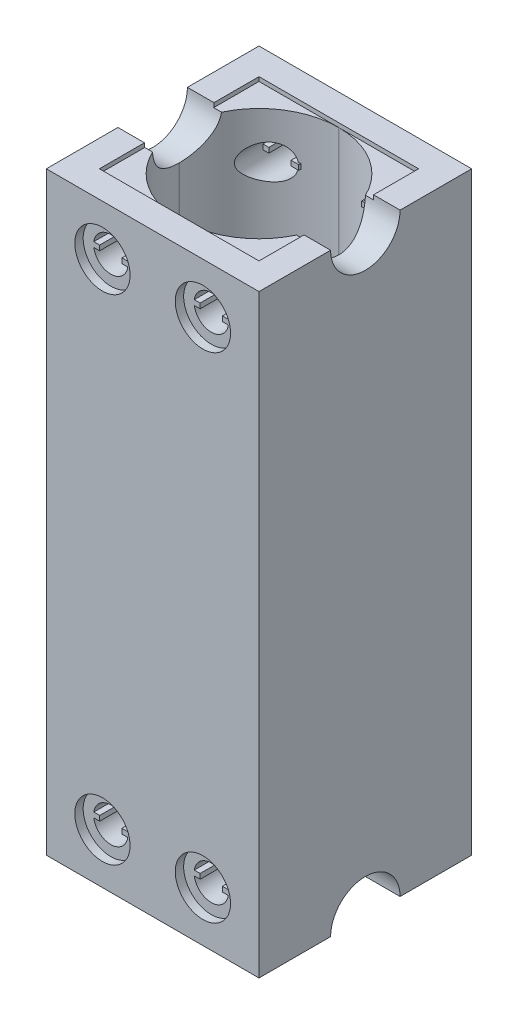
SolidWorks part; units mm, degrees
ref_plane "Front Plane" through (0, 0, 0) normal (0, 0, 1) x (1, 0, 0)
ref_plane "Top Plane" through (0, 0, 0) normal (0, 1, 0) x (1, 0, 0)
ref_plane "Right Plane" through (0, 0, 0) normal (1, 0, 0) x (0, 0, -1)
sketch "Sketch1" plane through (0, 0, 0) normal (0, 1, 0) x (1, 0, 0)
  line L0 (0, 0) -> (0, 21.2255) construction
  line L1 (0, 0) -> (25.5176, 0) construction
  line L2 (-9.525, 9.525) -> (-9.525, -9.525)
  line L3 (-12.7, 12.7) -> (12.7, 12.7)
  line L4 (-12.7, 12.7) -> (-12.7, -12.7)
  line L5 (-12.7, -12.7) -> (12.7, -12.7)
  line L6 (12.7, 12.7) -> (12.7, -12.7)
  line L7 (-9.525, -9.525) -> (9.525, -9.525)
  line L8 (9.525, 9.525) -> (9.525, -9.525)
  line L9 (-9.525, 9.525) -> (9.525, 9.525)
  dimension "D1" = 25.4
  dimension "D2" = 25.4
  dimension "D3" = 3.175
extrude "Boss-Extrude1" add sketch "Sketch1" along normal mid plane 71
sketch "Sketch2" plane through (0, 0, 12.7) normal (0, 0, -1) x (-1, 0, 0)
  line L0 (0, 0) -> (0, 30.8399) construction
  line L2 (-12.7, 35.5) -> (12.7, 35.5) construction
  circle A0 centre (-6, 29.5) radius 2.05
  circle A1 centre (6, 29.5) radius 2.05
  dimension "D1" = 4.1
  dimension "D2" = 6
  dimension "D3" = 12
extrude "Cut-Extrude1" cut sketch "Sketch2" along normal through all
ref_axis "Axis1" through (0, 32.3819, 0) along (0, -1, 0)
sketch "Sketch3" plane through (12.7, 0, 0) normal (1, 0, 0) x (0, 0, -1)
  line L0 (-12.7, -35.5) -> (12.7, -35.5) construction
  line L1 (-4.15, -35.5) -> (4.15, -35.5)
  arc A0 (4.15, -35.5) -> (-4.15, -35.5) centre (0, -35.5) ccw
  dimension "D1" = 8.3
extrude "Cut-Extrude2" cut sketch "Sketch3" against normal through all
mirror "Mirror2" about plane through (0, 0, 0) normal (0, 1, 0) of "Cut-Extrude2", "Cut-Extrude1"
sketch "Sketch9" plane through (0, 0, 12.7) normal (0, 0, 1) x (1, 0, 0)
  line L0 (-6, 29.5) -> (-6, 3.1588) construction
  line L1 (6, 29.5) -> (6, 3.1588) construction
  circle A0 centre (-6, 18) radius 2.05
  circle A1 centre (6, 18) radius 2.05
  circle A2 centre (-6, 29.5) radius 2.05 construction
  dimension "D1" = 11.5
fillet "Fillet1" radius 9.5 4 edges at (-9.525, 0, -9.525) (-9.525, 0, 9.525) (9.525, 0, 9.525) (9.525, 0, -9.525)
sketch "Sketch4" plane through (0, -35.5, 0) normal (0, 1, 0) x (1, 0, 0)
  line L0 (0, 0) -> (0, 13.3868) construction
  line L1 (0, 0) -> (17.4828, 0) construction
  circle A0 centre (7.78, -7.78) radius 1.175
  circle A1 centre (-7.78, -7.78) radius 1.175
  circle A2 centre (7.78, 7.78) radius 1.175
  circle A3 centre (-7.78, 7.78) radius 1.175
  dimension "D3" = 2.35
  dimension "D1" = 15.56
  dimension "D2" = 15.56
sketch "Sketch7" plane through (0, 35.5, 0) normal (0, 1, 0) x (1, 0, 0)
  line L0 (0, 0) -> (0, 13.6655) construction
  line L1 (0, 0) -> (18.6104, 0) construction
  line L3 (-9.53, 9.53) -> (9.53, 9.53)
  line L4 (-9.53, 9.53) -> (-9.53, -9.53)
  line L5 (-9.53, -9.53) -> (9.53, -9.53)
  line L6 (9.53, 9.53) -> (9.53, -9.53)
  dimension "D1" = 19.06
extrude "Cut-Extrude4" cut sketch "Sketch7" against normal blind 0.5
extrude "Cut-Extrude5" cut sketch "Sketch4" along normal blind 2.4
sketch "Sketch10" plane through (0, -35.5, 0) normal (0, -1, 0) x (1, 0, 0)
  circle A0 centre (-7.78, 7.78) radius 2.15 construction
  circle A1 centre (-7.78, 7.78) radius 3.75 construction
  dimension "D1" = 4.3
  dimension "D2" = 7.5
sketch "Sketch11" plane through (0, -35.5, 0) normal (0, -1, 0) x (1, 0, 0)
  line L0 (0, 0) -> (0, 13.4046) construction
  line L5 (0, 13.4046) -> (-0.0317, 13.4363) construction
  line L6 (0, 0) -> (16.0538, 0) construction
  line L7 (-7.78, 10.6668) -> (-10.28, 9.2234) construction
  line L8 (-10.28, 9.2234) -> (-10.28, 6.3366) construction
  line L9 (-10.28, 6.3366) -> (-7.78, 4.8932) construction
  line L10 (-7.78, 4.8932) -> (-5.28, 6.3366) construction
  line L11 (-5.28, 6.3366) -> (-5.28, 9.2234) construction
  line L12 (-5.28, 9.2234) -> (-7.78, 10.6668) construction
  line L13 (-5.18, 6.2789) -> (-5.18, 9.2811)
  line L14 (-5.18, 9.2811) -> (-7.78, 10.7822)
  line L15 (-7.78, 10.7822) -> (-10.38, 9.2811)
  line L16 (-10.38, 9.2811) -> (-10.38, 6.2789)
  line L17 (-10.38, 6.2789) -> (-7.78, 4.7778)
  line L18 (-7.78, 4.7778) -> (-5.18, 6.2789)
  line L19 (10.38, 6.2789) -> (7.78, 4.7778)
  line L20 (10.38, 9.2811) -> (10.38, 6.2789)
  line L21 (7.78, 10.7822) -> (10.38, 9.2811)
  line L22 (5.18, 9.2811) -> (7.78, 10.7822)
  line L23 (5.18, 6.2789) -> (5.18, 9.2811)
  line L24 (7.78, 4.7778) -> (5.18, 6.2789)
  line L25 (5.18, -9.2811) -> (7.78, -10.7822)
  line L26 (7.78, -10.7822) -> (10.38, -9.2811)
  line L27 (10.38, -9.2811) -> (10.38, -6.2789)
  line L28 (10.38, -6.2789) -> (7.78, -4.7778)
  line L29 (7.78, -4.7778) -> (5.18, -6.2789)
  line L30 (5.18, -6.2789) -> (5.18, -9.2811)
  line L31 (-10.38, -6.2789) -> (-7.78, -4.7778)
  line L32 (-10.38, -9.2811) -> (-10.38, -6.2789)
  line L33 (-7.78, -10.7822) -> (-10.38, -9.2811)
  line L34 (-5.18, -9.2811) -> (-7.78, -10.7822)
  line L35 (-5.18, -6.2789) -> (-5.18, -9.2811)
  line L36 (-7.78, -4.7778) -> (-5.18, -6.2789)
  circle A1 centre (-7.78, 7.78) radius 2.5 construction
  dimension "D2" = 5
  dimension "D3" = 120
  dimension "D4" = 120
  dimension "D5" = 120
  dimension "D6" = 120
  dimension "D7" = 0.1
extrude "Cut-Extrude8" cut sketch "Sketch11" against normal blind 2.4
ref_plane "Plane1" through (0, 0, 11.9) normal (0, 0, 1) x (1, 0, 0)
sketch "Sketch13" plane through (0, 0, 11.9) normal (0, 0, 1) x (1, 0, 0)
  line L0 (-6, 29.5) -> (-11.1534, 29.5) construction
  line L1 (-8.0279, 29.8) -> (-8.2444, 29.8)
  line L2 (-8.0279, 29.8) -> (-7.3279, 29.8)
  line L3 (-8.2444, 29.8) -> (-8.2444, 29.2)
  line L4 (-7.9774, 29.2) -> (-7.3279, 29.2)
  line L5 (-7.3279, 29.8) -> (-7.3279, 29.2)
  line L6 (-8.2444, 29.2) -> (-7.9774, 29.2)
  line L7 (-6, 29.5) -> (-6, 27.339) construction
  line L8 (0, 0) -> (0, 44.7414) construction
  line L9 (0, 0) -> (-23.4735, 0) construction
  line L10 (-3.9721, 29.8) -> (-3.7556, 29.8)
  line L11 (-4.6721, 29.8) -> (-4.6721, 29.2)
  line L12 (-3.9721, 29.8) -> (-4.6721, 29.8)
  line L13 (-3.7556, 29.8) -> (-3.7556, 29.2)
  line L14 (-3.7556, 29.2) -> (-4.0226, 29.2)
  line L15 (-4.0226, 29.2) -> (-4.6721, 29.2)
  line L16 (7.3279, 29.8) -> (7.3279, 29.2)
  line L17 (8.0279, 29.8) -> (7.3279, 29.8)
  line L18 (8.0279, 29.8) -> (8.2444, 29.8)
  line L19 (8.2444, 29.8) -> (8.2444, 29.2)
  line L20 (8.2444, 29.2) -> (7.9774, 29.2)
  line L21 (7.9774, 29.2) -> (7.3279, 29.2)
  line L22 (3.7556, 29.8) -> (3.7556, 29.2)
  line L23 (3.9721, 29.8) -> (3.7556, 29.8)
  line L24 (3.9721, 29.8) -> (4.6721, 29.8)
  line L25 (4.6721, 29.8) -> (4.6721, 29.2)
  line L26 (4.0226, 29.2) -> (4.6721, 29.2)
  line L27 (3.7556, 29.2) -> (4.0226, 29.2)
  line L28 (3.7556, -29.2) -> (4.0226, -29.2)
  line L29 (4.0226, -29.2) -> (4.6721, -29.2)
  line L30 (4.6721, -29.8) -> (4.6721, -29.2)
  line L31 (3.9721, -29.8) -> (4.6721, -29.8)
  line L32 (3.9721, -29.8) -> (3.7556, -29.8)
  line L33 (3.7556, -29.8) -> (3.7556, -29.2)
  line L34 (7.9774, -29.2) -> (7.3279, -29.2)
  line L35 (8.2444, -29.2) -> (7.9774, -29.2)
  line L36 (8.2444, -29.8) -> (8.2444, -29.2)
  line L37 (8.0279, -29.8) -> (8.2444, -29.8)
  line L38 (8.0279, -29.8) -> (7.3279, -29.8)
  line L39 (7.3279, -29.8) -> (7.3279, -29.2)
  line L40 (-4.0226, -29.2) -> (-4.6721, -29.2)
  line L41 (-3.7556, -29.2) -> (-4.0226, -29.2)
  line L42 (-3.7556, -29.8) -> (-3.7556, -29.2)
  line L43 (-3.9721, -29.8) -> (-4.6721, -29.8)
  line L44 (-4.6721, -29.8) -> (-4.6721, -29.2)
  line L45 (-3.9721, -29.8) -> (-3.7556, -29.8)
  line L46 (-8.2444, -29.2) -> (-7.9774, -29.2)
  line L47 (-7.3279, -29.8) -> (-7.3279, -29.2)
  line L48 (-7.9774, -29.2) -> (-7.3279, -29.2)
  line L49 (-8.2444, -29.8) -> (-8.2444, -29.2)
  line L50 (-8.0279, -29.8) -> (-7.3279, -29.8)
  line L51 (-8.0279, -29.8) -> (-8.2444, -29.8)
  circle A1 centre (-6, 29.5) radius 2.05 construction
  dimension "D1" = 0.6
  dimension "D2" = 0.7
extrude "Boss-Extrude3" add sketch "Sketch13" against normal blind 3.4
mirror "Mirror3" about plane through (0, 0, 0) normal (0, 0, 1) of "Boss-Extrude3"
sketch "Sketch15" plane through (0, 0, 12.7) normal (0, 0, 1) x (1, 0, 0)
  circle A0 centre (6, 27.9125) radius 1.35 construction
  circle A1 centre (6, 29.5) radius 2.05 construction
  dimension "D1" = 2.7
  dimension "D2" = 1.5875
sketch "Sketch16" plane through (0, 0, 12.7) normal (0, 0, 1) x (1, 0, 0)
  circle A0 centre (-6, 29.5) radius 3.3
  circle A1 centre (6, 29.5) radius 3.3
  circle A2 centre (-6, -29.5) radius 3.3
  circle A3 centre (6, -29.5) radius 3.3
  dimension "D1" = 6.6
extrude "Cut-Extrude9" cut sketch "Sketch16" against normal blind 1
mirror "Mirror4" about plane through (0, 0, 0) normal (0, 0, 1) of "Cut-Extrude9"
